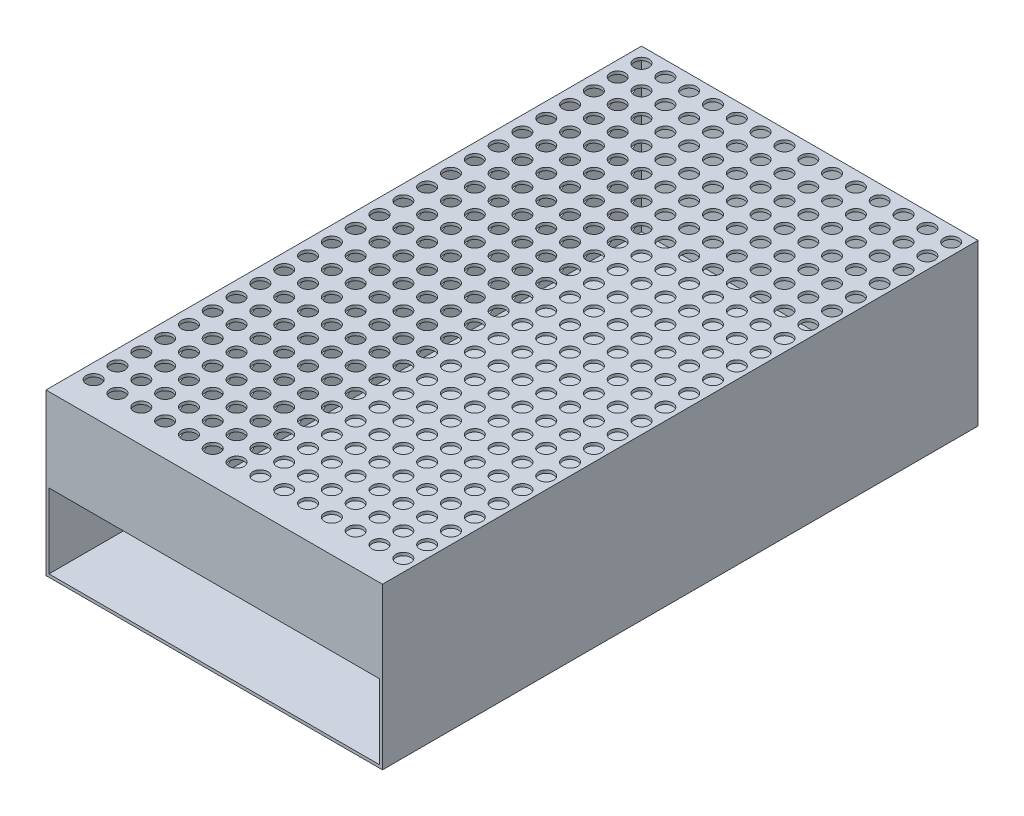
SolidWorks part; units mm, degrees
ref_plane "Front Plane" through (0, 0, 0) normal (0, 0, 1) x (1, 0, 0)
ref_plane "Top Plane" through (0, 0, 0) normal (0, 1, 0) x (1, 0, 0)
ref_plane "Right Plane" through (0, 0, 0) normal (1, 0, 0) x (0, 0, -1)
sketch "Sketch1" plane through (0, 0, 0) normal (0, 1, 0) x (1, 0, 0)
  line L1 (56.5, 100) -> (-56.5, 100)
  line L2 (56.5, 100) -> (56.5, -100)
  line L3 (56.5, -100) -> (-56.5, -100)
  line L4 (-56.5, 100) -> (-56.5, -100)
  line L5 (56.5, 100) -> (-56.5, -100) construction
  line L6 (56.5, -100) -> (-56.5, 100) construction
  point P0 (0, 0)
  dimension "D1" = 200
  dimension "D2" = 113
extrude "Boss-Extrude1" add sketch "Sketch1" along normal blind 54
sketch "Sketch3" plane through (0, 0, 100) normal (0, 0, 1) x (1, 0, 0)
  line L8 (-55.5, 1) -> (55.5, 1)
  line L9 (55.5, 1) -> (55.5, 53)
  line L10 (55.5, 53) -> (-55.5, 53)
  line L11 (-55.5, 53) -> (-55.5, 1)
  line L12 (-55.5, 1) -> (55.5, 1)
  line L13 (55.5, 1) -> (55.5, 53)
  line L14 (55.5, 53) -> (-55.5, 53)
  line L15 (-55.5, 53) -> (-55.5, 1)
  dimension "D1" = 1
extrude "Cut-Extrude1" cut sketch "Sketch3" against normal blind 199
sketch "Sketch4" plane through (-56.5, 0, 0) normal (-1, 0, 0) x (0, 0, 1)
  line L0 (-100, 0) -> (100, 0) construction
  line L1 (-100, 54) -> (-100, 0) construction
  circle A0 centre (-95, 5) radius 2.5
  circle A1 centre (-87, 5) radius 2.5
  circle A2 centre (-79, 5) radius 2.5
  circle A3 centre (-71, 5) radius 2.5
  circle A4 centre (-63, 5) radius 2.5
  circle A5 centre (-55, 5) radius 2.5
  circle A6 centre (-47, 5) radius 2.5
  circle A7 centre (-39, 5) radius 2.5
  circle A8 centre (-31, 5) radius 2.5
  circle A9 centre (-23, 5) radius 2.5
  circle A10 centre (-15, 5) radius 2.5
  circle A11 centre (-7, 5) radius 2.5
  circle A12 centre (1, 5) radius 2.5
  circle A13 centre (9, 5) radius 2.5
  circle A14 centre (17, 5) radius 2.5
  circle A15 centre (25, 5) radius 2.5
  circle A16 centre (33, 5) radius 2.5
  circle A17 centre (41, 5) radius 2.5
  circle A18 centre (49, 5) radius 2.5
  circle A19 centre (57, 5) radius 2.5
  circle A20 centre (-87, 13) radius 2.5
  circle A21 centre (-79, 13) radius 2.5
  circle A22 centre (-71, 13) radius 2.5
  circle A23 centre (-63, 13) radius 2.5
  circle A24 centre (-55, 13) radius 2.5
  circle A25 centre (-47, 13) radius 2.5
  circle A26 centre (-39, 13) radius 2.5
  circle A27 centre (-31, 13) radius 2.5
  circle A28 centre (-23, 13) radius 2.5
  circle A29 centre (-15, 13) radius 2.5
  circle A30 centre (-7, 13) radius 2.5
  circle A31 centre (1, 13) radius 2.5
  circle A32 centre (9, 13) radius 2.5
  circle A33 centre (17, 13) radius 2.5
  circle A34 centre (25, 13) radius 2.5
  circle A35 centre (33, 13) radius 2.5
  circle A36 centre (41, 13) radius 2.5
  circle A37 centre (49, 13) radius 2.5
  circle A38 centre (57, 13) radius 2.5
  circle A39 centre (-87, 21) radius 2.5
  circle A40 centre (-79, 21) radius 2.5
  circle A41 centre (-71, 21) radius 2.5
  circle A42 centre (-63, 21) radius 2.5
  circle A43 centre (-55, 21) radius 2.5
  circle A44 centre (-47, 21) radius 2.5
  circle A45 centre (-39, 21) radius 2.5
  circle A46 centre (-31, 21) radius 2.5
  circle A47 centre (-23, 21) radius 2.5
  circle A48 centre (-15, 21) radius 2.5
  circle A49 centre (-7, 21) radius 2.5
  circle A50 centre (1, 21) radius 2.5
  circle A51 centre (9, 21) radius 2.5
  circle A52 centre (17, 21) radius 2.5
  circle A53 centre (25, 21) radius 2.5
  circle A54 centre (33, 21) radius 2.5
  circle A55 centre (41, 21) radius 2.5
  circle A56 centre (49, 21) radius 2.5
  circle A57 centre (57, 21) radius 2.5
  circle A58 centre (-87, 29) radius 2.5
  circle A59 centre (-79, 29) radius 2.5
  circle A60 centre (-71, 29) radius 2.5
  circle A61 centre (-63, 29) radius 2.5
  circle A62 centre (-55, 29) radius 2.5
  circle A63 centre (-47, 29) radius 2.5
  circle A64 centre (-39, 29) radius 2.5
  circle A65 centre (-31, 29) radius 2.5
  circle A66 centre (-23, 29) radius 2.5
  circle A67 centre (-15, 29) radius 2.5
  circle A68 centre (-7, 29) radius 2.5
  circle A69 centre (1, 29) radius 2.5
  circle A70 centre (9, 29) radius 2.5
  circle A71 centre (17, 29) radius 2.5
  circle A72 centre (25, 29) radius 2.5
  circle A73 centre (33, 29) radius 2.5
  circle A74 centre (41, 29) radius 2.5
  circle A75 centre (49, 29) radius 2.5
  circle A76 centre (57, 29) radius 2.5
  circle A77 centre (-87, 37) radius 2.5
  circle A78 centre (-79, 37) radius 2.5
  circle A79 centre (-71, 37) radius 2.5
  circle A80 centre (-63, 37) radius 2.5
  circle A81 centre (-55, 37) radius 2.5
  circle A82 centre (-47, 37) radius 2.5
  circle A83 centre (-39, 37) radius 2.5
  circle A84 centre (-31, 37) radius 2.5
  circle A85 centre (-23, 37) radius 2.5
  circle A86 centre (-15, 37) radius 2.5
  circle A87 centre (-7, 37) radius 2.5
  circle A88 centre (1, 37) radius 2.5
  circle A89 centre (9, 37) radius 2.5
  circle A90 centre (17, 37) radius 2.5
  circle A91 centre (25, 37) radius 2.5
  circle A92 centre (33, 37) radius 2.5
  circle A93 centre (41, 37) radius 2.5
  circle A94 centre (49, 37) radius 2.5
  circle A95 centre (57, 37) radius 2.5
  circle A96 centre (-87, 45) radius 2.5
  circle A97 centre (-79, 45) radius 2.5
  circle A98 centre (-71, 45) radius 2.5
  circle A99 centre (-63, 45) radius 2.5
  circle A100 centre (-55, 45) radius 2.5
  circle A101 centre (-47, 45) radius 2.5
  circle A102 centre (-39, 45) radius 2.5
  circle A103 centre (-31, 45) radius 2.5
  circle A104 centre (-23, 45) radius 2.5
  circle A105 centre (-15, 45) radius 2.5
  circle A106 centre (-7, 45) radius 2.5
  circle A107 centre (1, 45) radius 2.5
  circle A108 centre (9, 45) radius 2.5
  circle A109 centre (17, 45) radius 2.5
  circle A110 centre (25, 45) radius 2.5
  circle A111 centre (33, 45) radius 2.5
  circle A112 centre (41, 45) radius 2.5
  circle A113 centre (49, 45) radius 2.5
  circle A114 centre (57, 45) radius 2.5
  circle A115 centre (-95, 13) radius 2.5
  circle A116 centre (-95, 21) radius 2.5
  circle A117 centre (-95, 29) radius 2.5
  circle A118 centre (-95, 37) radius 2.5
  circle A119 centre (-95, 45) radius 2.5
  dimension "D3" = 5
  dimension "D1" = 5
  dimension "D2" = 5
  dimension "D4" = 20
  dimension "D5" = 6
extrude "Cut-Extrude2" cut sketch "Sketch4" against normal blind 65
sketch "Sketch5" plane through (0, 54, 0) normal (0, 1, 0) x (1, 0, 0)
  line L0 (-56.5, 100) -> (-56.5, -100) construction
  line L1 (56.5, 100) -> (-56.5, 100) construction
  circle A0 centre (-51.5, 95) radius 2.5
  circle A1 centre (-43.5, 95) radius 2.5
  circle A2 centre (-35.5, 95) radius 2.5
  circle A3 centre (-27.5, 95) radius 2.5
  circle A4 centre (-19.5, 95) radius 2.5
  circle A5 centre (-11.5, 95) radius 2.5
  circle A6 centre (-3.5, 95) radius 2.5
  circle A7 centre (4.5, 95) radius 2.5
  circle A8 centre (12.5, 95) radius 2.5
  circle A9 centre (20.5, 95) radius 2.5
  circle A10 centre (28.5, 95) radius 2.5
  circle A11 centre (36.5, 95) radius 2.5
  circle A12 centre (44.5, 95) radius 2.5
  circle A13 centre (52.5, 95) radius 2.5
  circle A14 centre (-43.5, 87) radius 2.5
  circle A15 centre (-35.5, 87) radius 2.5
  circle A16 centre (-27.5, 87) radius 2.5
  circle A17 centre (-19.5, 87) radius 2.5
  circle A18 centre (-11.5, 87) radius 2.5
  circle A19 centre (-3.5, 87) radius 2.5
  circle A20 centre (4.5, 87) radius 2.5
  circle A21 centre (12.5, 87) radius 2.5
  circle A22 centre (20.5, 87) radius 2.5
  circle A23 centre (28.5, 87) radius 2.5
  circle A24 centre (36.5, 87) radius 2.5
  circle A25 centre (44.5, 87) radius 2.5
  circle A26 centre (52.5, 87) radius 2.5
  circle A27 centre (-43.5, 79) radius 2.5
  circle A28 centre (-35.5, 79) radius 2.5
  circle A29 centre (-27.5, 79) radius 2.5
  circle A30 centre (-19.5, 79) radius 2.5
  circle A31 centre (-11.5, 79) radius 2.5
  circle A32 centre (-3.5, 79) radius 2.5
  circle A33 centre (4.5, 79) radius 2.5
  circle A34 centre (12.5, 79) radius 2.5
  circle A35 centre (20.5, 79) radius 2.5
  circle A36 centre (28.5, 79) radius 2.5
  circle A37 centre (36.5, 79) radius 2.5
  circle A38 centre (44.5, 79) radius 2.5
  circle A39 centre (52.5, 79) radius 2.5
  circle A40 centre (-43.5, 71) radius 2.5
  circle A41 centre (-35.5, 71) radius 2.5
  circle A42 centre (-27.5, 71) radius 2.5
  circle A43 centre (-19.5, 71) radius 2.5
  circle A44 centre (-11.5, 71) radius 2.5
  circle A45 centre (-3.5, 71) radius 2.5
  circle A46 centre (4.5, 71) radius 2.5
  circle A47 centre (12.5, 71) radius 2.5
  circle A48 centre (20.5, 71) radius 2.5
  circle A49 centre (28.5, 71) radius 2.5
  circle A50 centre (36.5, 71) radius 2.5
  circle A51 centre (44.5, 71) radius 2.5
  circle A52 centre (52.5, 71) radius 2.5
  circle A53 centre (-43.5, 63) radius 2.5
  circle A54 centre (-35.5, 63) radius 2.5
  circle A55 centre (-27.5, 63) radius 2.5
  circle A56 centre (-19.5, 63) radius 2.5
  circle A57 centre (-11.5, 63) radius 2.5
  circle A58 centre (-3.5, 63) radius 2.5
  circle A59 centre (4.5, 63) radius 2.5
  circle A60 centre (12.5, 63) radius 2.5
  circle A61 centre (20.5, 63) radius 2.5
  circle A62 centre (28.5, 63) radius 2.5
  circle A63 centre (36.5, 63) radius 2.5
  circle A64 centre (44.5, 63) radius 2.5
  circle A65 centre (52.5, 63) radius 2.5
  circle A66 centre (-43.5, 55) radius 2.5
  circle A67 centre (-35.5, 55) radius 2.5
  circle A68 centre (-27.5, 55) radius 2.5
  circle A69 centre (-19.5, 55) radius 2.5
  circle A70 centre (-11.5, 55) radius 2.5
  circle A71 centre (-3.5, 55) radius 2.5
  circle A72 centre (4.5, 55) radius 2.5
  circle A73 centre (12.5, 55) radius 2.5
  circle A74 centre (20.5, 55) radius 2.5
  circle A75 centre (28.5, 55) radius 2.5
  circle A76 centre (36.5, 55) radius 2.5
  circle A77 centre (44.5, 55) radius 2.5
  circle A78 centre (52.5, 55) radius 2.5
  circle A79 centre (-43.5, 47) radius 2.5
  circle A80 centre (-35.5, 47) radius 2.5
  circle A81 centre (-27.5, 47) radius 2.5
  circle A82 centre (-19.5, 47) radius 2.5
  circle A83 centre (-11.5, 47) radius 2.5
  circle A84 centre (-3.5, 47) radius 2.5
  circle A85 centre (4.5, 47) radius 2.5
  circle A86 centre (12.5, 47) radius 2.5
  circle A87 centre (20.5, 47) radius 2.5
  circle A88 centre (28.5, 47) radius 2.5
  circle A89 centre (36.5, 47) radius 2.5
  circle A90 centre (44.5, 47) radius 2.5
  circle A91 centre (52.5, 47) radius 2.5
  circle A92 centre (-43.5, 39) radius 2.5
  circle A93 centre (-35.5, 39) radius 2.5
  circle A94 centre (-27.5, 39) radius 2.5
  circle A95 centre (-19.5, 39) radius 2.5
  circle A96 centre (-11.5, 39) radius 2.5
  circle A97 centre (-3.5, 39) radius 2.5
  circle A98 centre (4.5, 39) radius 2.5
  circle A99 centre (12.5, 39) radius 2.5
  circle A100 centre (20.5, 39) radius 2.5
  circle A101 centre (28.5, 39) radius 2.5
  circle A102 centre (36.5, 39) radius 2.5
  circle A103 centre (44.5, 39) radius 2.5
  circle A104 centre (52.5, 39) radius 2.5
  circle A105 centre (-43.5, 31) radius 2.5
  circle A106 centre (-35.5, 31) radius 2.5
  circle A107 centre (-27.5, 31) radius 2.5
  circle A108 centre (-19.5, 31) radius 2.5
  circle A109 centre (-11.5, 31) radius 2.5
  circle A110 centre (-3.5, 31) radius 2.5
  circle A111 centre (4.5, 31) radius 2.5
  circle A112 centre (12.5, 31) radius 2.5
  circle A113 centre (20.5, 31) radius 2.5
  circle A114 centre (28.5, 31) radius 2.5
  circle A115 centre (36.5, 31) radius 2.5
  circle A116 centre (44.5, 31) radius 2.5
  circle A117 centre (52.5, 31) radius 2.5
  circle A118 centre (-43.5, 23) radius 2.5
  circle A119 centre (-35.5, 23) radius 2.5
  circle A120 centre (-27.5, 23) radius 2.5
  circle A121 centre (-19.5, 23) radius 2.5
  circle A122 centre (-11.5, 23) radius 2.5
  circle A123 centre (-3.5, 23) radius 2.5
  circle A124 centre (4.5, 23) radius 2.5
  circle A125 centre (12.5, 23) radius 2.5
  circle A126 centre (20.5, 23) radius 2.5
  circle A127 centre (28.5, 23) radius 2.5
  circle A128 centre (36.5, 23) radius 2.5
  circle A129 centre (44.5, 23) radius 2.5
  circle A130 centre (52.5, 23) radius 2.5
  circle A131 centre (-43.5, 15) radius 2.5
  circle A132 centre (-35.5, 15) radius 2.5
  circle A133 centre (-27.5, 15) radius 2.5
  circle A134 centre (-19.5, 15) radius 2.5
  circle A135 centre (-11.5, 15) radius 2.5
  circle A136 centre (-3.5, 15) radius 2.5
  circle A137 centre (4.5, 15) radius 2.5
  circle A138 centre (12.5, 15) radius 2.5
  circle A139 centre (20.5, 15) radius 2.5
  circle A140 centre (28.5, 15) radius 2.5
  circle A141 centre (36.5, 15) radius 2.5
  circle A142 centre (44.5, 15) radius 2.5
  circle A143 centre (52.5, 15) radius 2.5
  circle A144 centre (-43.5, 7) radius 2.5
  circle A145 centre (-35.5, 7) radius 2.5
  circle A146 centre (-27.5, 7) radius 2.5
  circle A147 centre (-19.5, 7) radius 2.5
  circle A148 centre (-11.5, 7) radius 2.5
  circle A149 centre (-3.5, 7) radius 2.5
  circle A150 centre (4.5, 7) radius 2.5
  circle A151 centre (12.5, 7) radius 2.5
  circle A152 centre (20.5, 7) radius 2.5
  circle A153 centre (28.5, 7) radius 2.5
  circle A154 centre (36.5, 7) radius 2.5
  circle A155 centre (44.5, 7) radius 2.5
  circle A156 centre (52.5, 7) radius 2.5
  circle A157 centre (-43.5, -1) radius 2.5
  circle A158 centre (-35.5, -1) radius 2.5
  circle A159 centre (-27.5, -1) radius 2.5
  circle A160 centre (-19.5, -1) radius 2.5
  circle A161 centre (-11.5, -1) radius 2.5
  circle A162 centre (-3.5, -1) radius 2.5
  circle A163 centre (4.5, -1) radius 2.5
  circle A164 centre (12.5, -1) radius 2.5
  circle A165 centre (20.5, -1) radius 2.5
  circle A166 centre (28.5, -1) radius 2.5
  circle A167 centre (36.5, -1) radius 2.5
  circle A168 centre (44.5, -1) radius 2.5
  circle A169 centre (52.5, -1) radius 2.5
  circle A170 centre (-43.5, -9) radius 2.5
  circle A171 centre (-35.5, -9) radius 2.5
  circle A172 centre (-27.5, -9) radius 2.5
  circle A173 centre (-19.5, -9) radius 2.5
  circle A174 centre (-11.5, -9) radius 2.5
  circle A175 centre (-3.5, -9) radius 2.5
  circle A176 centre (4.5, -9) radius 2.5
  circle A177 centre (12.5, -9) radius 2.5
  circle A178 centre (20.5, -9) radius 2.5
  circle A179 centre (28.5, -9) radius 2.5
  circle A180 centre (36.5, -9) radius 2.5
  circle A181 centre (44.5, -9) radius 2.5
  circle A182 centre (52.5, -9) radius 2.5
  circle A183 centre (-43.5, -17) radius 2.5
  circle A184 centre (-35.5, -17) radius 2.5
  circle A185 centre (-27.5, -17) radius 2.5
  circle A186 centre (-19.5, -17) radius 2.5
  circle A187 centre (-11.5, -17) radius 2.5
  circle A188 centre (-3.5, -17) radius 2.5
  circle A189 centre (4.5, -17) radius 2.5
  circle A190 centre (12.5, -17) radius 2.5
  circle A191 centre (20.5, -17) radius 2.5
  circle A192 centre (28.5, -17) radius 2.5
  circle A193 centre (36.5, -17) radius 2.5
  circle A194 centre (44.5, -17) radius 2.5
  circle A195 centre (52.5, -17) radius 2.5
  circle A196 centre (-43.5, -25) radius 2.5
  circle A197 centre (-35.5, -25) radius 2.5
  circle A198 centre (-27.5, -25) radius 2.5
  circle A199 centre (-19.5, -25) radius 2.5
  circle A200 centre (-11.5, -25) radius 2.5
  circle A201 centre (-3.5, -25) radius 2.5
  circle A202 centre (4.5, -25) radius 2.5
  circle A203 centre (12.5, -25) radius 2.5
  circle A204 centre (20.5, -25) radius 2.5
  circle A205 centre (28.5, -25) radius 2.5
  circle A206 centre (36.5, -25) radius 2.5
  circle A207 centre (44.5, -25) radius 2.5
  circle A208 centre (52.5, -25) radius 2.5
  circle A209 centre (-43.5, -33) radius 2.5
  circle A210 centre (-35.5, -33) radius 2.5
  circle A211 centre (-27.5, -33) radius 2.5
  circle A212 centre (-19.5, -33) radius 2.5
  circle A213 centre (-11.5, -33) radius 2.5
  circle A214 centre (-3.5, -33) radius 2.5
  circle A215 centre (4.5, -33) radius 2.5
  circle A216 centre (12.5, -33) radius 2.5
  circle A217 centre (20.5, -33) radius 2.5
  circle A218 centre (28.5, -33) radius 2.5
  circle A219 centre (36.5, -33) radius 2.5
  circle A220 centre (44.5, -33) radius 2.5
  circle A221 centre (52.5, -33) radius 2.5
  circle A222 centre (-43.5, -41) radius 2.5
  circle A223 centre (-35.5, -41) radius 2.5
  circle A224 centre (-27.5, -41) radius 2.5
  circle A225 centre (-19.5, -41) radius 2.5
  circle A226 centre (-11.5, -41) radius 2.5
  circle A227 centre (-3.5, -41) radius 2.5
  circle A228 centre (4.5, -41) radius 2.5
  circle A229 centre (12.5, -41) radius 2.5
  circle A230 centre (20.5, -41) radius 2.5
  circle A231 centre (28.5, -41) radius 2.5
  circle A232 centre (36.5, -41) radius 2.5
  circle A233 centre (44.5, -41) radius 2.5
  circle A234 centre (52.5, -41) radius 2.5
  circle A235 centre (-43.5, -49) radius 2.5
  circle A236 centre (-35.5, -49) radius 2.5
  circle A237 centre (-27.5, -49) radius 2.5
  circle A238 centre (-19.5, -49) radius 2.5
  circle A239 centre (-11.5, -49) radius 2.5
  circle A240 centre (-3.5, -49) radius 2.5
  circle A241 centre (4.5, -49) radius 2.5
  circle A242 centre (12.5, -49) radius 2.5
  circle A243 centre (20.5, -49) radius 2.5
  circle A244 centre (28.5, -49) radius 2.5
  circle A245 centre (36.5, -49) radius 2.5
  circle A246 centre (44.5, -49) radius 2.5
  circle A247 centre (52.5, -49) radius 2.5
  circle A248 centre (-43.5, -57) radius 2.5
  circle A249 centre (-35.5, -57) radius 2.5
  circle A250 centre (-27.5, -57) radius 2.5
  circle A251 centre (-19.5, -57) radius 2.5
  circle A252 centre (-11.5, -57) radius 2.5
  circle A253 centre (-3.5, -57) radius 2.5
  circle A254 centre (4.5, -57) radius 2.5
  circle A255 centre (12.5, -57) radius 2.5
  circle A256 centre (20.5, -57) radius 2.5
  circle A257 centre (28.5, -57) radius 2.5
  circle A258 centre (36.5, -57) radius 2.5
  circle A259 centre (44.5, -57) radius 2.5
  circle A260 centre (52.5, -57) radius 2.5
  circle A261 centre (-43.5, -65) radius 2.5
  circle A262 centre (-35.5, -65) radius 2.5
  circle A263 centre (-27.5, -65) radius 2.5
  circle A264 centre (-19.5, -65) radius 2.5
  circle A265 centre (-11.5, -65) radius 2.5
  circle A266 centre (-3.5, -65) radius 2.5
  circle A267 centre (4.5, -65) radius 2.5
  circle A268 centre (12.5, -65) radius 2.5
  circle A269 centre (20.5, -65) radius 2.5
  circle A270 centre (28.5, -65) radius 2.5
  circle A271 centre (36.5, -65) radius 2.5
  circle A272 centre (44.5, -65) radius 2.5
  circle A273 centre (52.5, -65) radius 2.5
  circle A274 centre (-43.5, -73) radius 2.5
  circle A275 centre (-35.5, -73) radius 2.5
  circle A276 centre (-27.5, -73) radius 2.5
  circle A277 centre (-19.5, -73) radius 2.5
  circle A278 centre (-11.5, -73) radius 2.5
  circle A279 centre (-3.5, -73) radius 2.5
  circle A280 centre (4.5, -73) radius 2.5
  circle A281 centre (12.5, -73) radius 2.5
  circle A282 centre (20.5, -73) radius 2.5
  circle A283 centre (28.5, -73) radius 2.5
  circle A284 centre (36.5, -73) radius 2.5
  circle A285 centre (44.5, -73) radius 2.5
  circle A286 centre (52.5, -73) radius 2.5
  circle A287 centre (-43.5, -81) radius 2.5
  circle A288 centre (-35.5, -81) radius 2.5
  circle A289 centre (-27.5, -81) radius 2.5
  circle A290 centre (-19.5, -81) radius 2.5
  circle A291 centre (-11.5, -81) radius 2.5
  circle A292 centre (-3.5, -81) radius 2.5
  circle A293 centre (4.5, -81) radius 2.5
  circle A294 centre (12.5, -81) radius 2.5
  circle A295 centre (20.5, -81) radius 2.5
  circle A296 centre (28.5, -81) radius 2.5
  circle A297 centre (36.5, -81) radius 2.5
  circle A298 centre (44.5, -81) radius 2.5
  circle A299 centre (52.5, -81) radius 2.5
  circle A300 centre (-43.5, -89) radius 2.5
  circle A301 centre (-35.5, -89) radius 2.5
  circle A302 centre (-27.5, -89) radius 2.5
  circle A303 centre (-19.5, -89) radius 2.5
  circle A304 centre (-11.5, -89) radius 2.5
  circle A305 centre (-3.5, -89) radius 2.5
  circle A306 centre (4.5, -89) radius 2.5
  circle A307 centre (12.5, -89) radius 2.5
  circle A308 centre (20.5, -89) radius 2.5
  circle A309 centre (28.5, -89) radius 2.5
  circle A310 centre (36.5, -89) radius 2.5
  circle A311 centre (44.5, -89) radius 2.5
  circle A312 centre (52.5, -89) radius 2.5
  circle A313 centre (-51.5, 87) radius 2.5
  circle A314 centre (-51.5, 79) radius 2.5
  circle A315 centre (-51.5, 71) radius 2.5
  circle A316 centre (-51.5, 63) radius 2.5
  circle A317 centre (-51.5, 55) radius 2.5
  circle A318 centre (-51.5, 47) radius 2.5
  circle A319 centre (-51.5, 39) radius 2.5
  circle A320 centre (-51.5, 31) radius 2.5
  circle A321 centre (-51.5, 23) radius 2.5
  circle A322 centre (-51.5, 15) radius 2.5
  circle A323 centre (-51.5, 7) radius 2.5
  circle A324 centre (-51.5, -1) radius 2.5
  circle A325 centre (-51.5, -9) radius 2.5
  circle A326 centre (-51.5, -17) radius 2.5
  circle A327 centre (-51.5, -25) radius 2.5
  circle A328 centre (-51.5, -33) radius 2.5
  circle A329 centre (-51.5, -41) radius 2.5
  circle A330 centre (-51.5, -49) radius 2.5
  circle A331 centre (-51.5, -57) radius 2.5
  circle A332 centre (-51.5, -65) radius 2.5
  circle A333 centre (-51.5, -73) radius 2.5
  circle A334 centre (-51.5, -81) radius 2.5
  circle A335 centre (-51.5, -89) radius 2.5
  point P6 (0, 0)
  dimension "D1" = 5
  dimension "D2" = 5
  dimension "D3" = 5
  dimension "D4" = 14
  dimension "D5" = 24
extrude "Cut-Extrude3" cut sketch "Sketch5" against normal blind 37
sketch "Sketch6" plane through (0, 53, 0) normal (0, -1, 0) x (1, 0, 0)
  line L0 (56.5, 100) -> (56.5, -100) construction
  line L1 (-56.5, 100) -> (56.5, 100)
  line L2 (-56.5, 100) -> (-56.5, 99)
  line L3 (-56.5, 99) -> (56.5, 99)
  line L4 (56.5, 100) -> (56.5, 99)
  dimension "D1" = 1
extrude "Boss-Extrude2" add sketch "Sketch6" along normal blind 27
